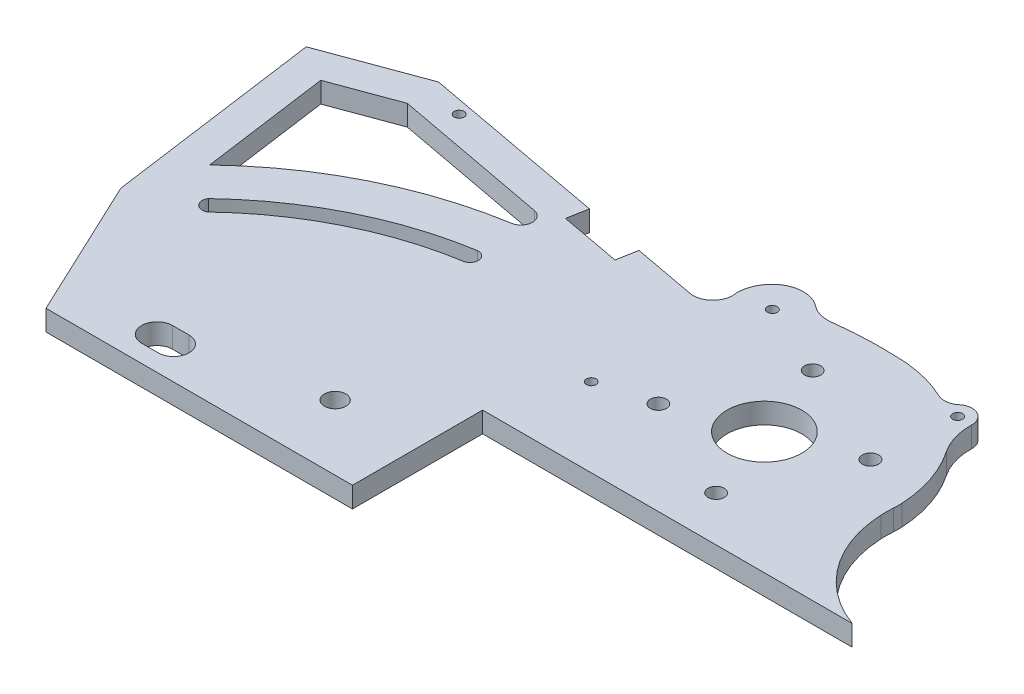
SolidWorks part; units mm, degrees
ref_plane "Front Plane" through (0, 0, 0) normal (0, 0, 1) x (1, 0, 0)
ref_plane "Top Plane" through (0, 0, 0) normal (0, 1, 0) x (1, 0, 0)
ref_plane "Right Plane" through (0, 0, 0) normal (1, 0, 0) x (0, 0, -1)
sketch "Sketch1" plane through (0, 0, 0) normal (0, 1, 0) x (1, 0, 0)
  line L0 (-48.99, 25.5713) -> (-67.7205, 29.0455)
  line L1 (-142.6426, 42.9422) -> (-143.5111, 38.2596) construction
  line L2 (-49.2049, -37.6819) -> (-49.2049, -77.8139)
  line L3 (-49.2049, -77.8139) -> (-76.5633, -77.8139)
  line L4 (-142.7166, 32.6227) -> (-162.215, 25.4248)
  line L5 (-162.215, 25.4248) -> (-156.7262, -14.2919)
  line L6 (-49.2049, -37.6819) -> (45.278, -37.6819)
  line L7 (-143.6125, 43.1221) -> (-173.3978, 32.1269)
  line L8 (-173.3978, 32.1269) -> (-164.2302, -34.2094)
  line L9 (-94.5199, 23.5914) -> (-142.7166, 32.6227)
  line L10 (-106.3396, 29.7503) -> (-50.148, 19.3278) construction
  line L11 (-143.6515, 36.6711) -> (-145.7426, 42.3358) construction
  line L12 (-50.148, 19.3278) -> (-48.99, 25.5713) construction
  line L13 (-143.6515, 36.6711) -> (-172.5514, 26.0027) construction
  line L14 (-123.3865, 39.3706) -> (-105.1816, 35.9938)
  line L15 (-142.7166, 32.6227) -> (-141.2552, 40.5019) construction
  line L18 (-86.451, 32.5197) -> (-87.6091, 26.2762)
  line L19 (-68.8786, 22.802) -> (-67.7205, 29.0455)
  line L20 (-86.451, 32.5197) -> (-105.1816, 35.9938)
  line L21 (-87.6091, 26.2762) -> (-68.8786, 22.802)
  line L22 (-164.2302, -34.2094) -> (-143.6929, -77.8139)
  line L23 (-143.6929, -77.8139) -> (-76.5633, -77.8139)
  line L24 (-114.5088, -67.653) -> (-119.5888, -67.653) construction
  line L25 (-114.5088, -72.4155) -> (-119.5888, -72.4155)
  line L26 (-114.5088, -62.8905) -> (-119.5888, -62.8905)
  line L29 (0, 0) -> (-57.1922, -21.2464) construction
  line L30 (-117.0488, -67.653) -> (-117.0488, -101.5353) construction
  line L31 (-49.2049, -37.6819) -> (45.278, -37.6819) construction
  line L32 (-49.2049, -37.6819) -> (45.278, -37.6819) construction
  line L33 (-49.2049, -37.6819) -> (45.278, -37.6819) construction
  line L34 (45.278, -37.6819) -> (64.7267, -37.6819)
  line L35 (-123.3865, 39.3706) -> (-143.6125, 43.1221)
  arc A0 (-48.99, 25.5713) -> (-41.3602, 32.7203) centre (-47.3631, 31.4809) ccw
  circle A1 centre (-131.8085, 37.7035) radius 1.524
  arc A2 (40.3286, 2.1532) -> (33.4191, 22.6758) centre (0, 0) ccw
  circle A3 centre (-131.8085, 37.7035) radius 1.1303 construction
  arc A4 (0, 40.386) -> (-18.9447, 39.5692) centre (-4.6204, -72.5606) ccw
  arc A5 (-38.2002, 40.515) -> (-41.3602, 32.7203) centre (-30.3114, 32.779) ccw
  arc A6 (-114.5088, -72.4155) -> (-114.5088, -62.8905) centre (-114.5088, -67.653) ccw
  circle A7 centre (-31.3995, 33.846) radius 1.524
  circle A8 centre (-31.3995, 33.846) radius 6.35 construction
  arc A9 (-25.5638, 41.374) -> (-38.2002, 40.515) centre (-31.3995, 33.846) ccw
  circle A10 centre (-23.7889, -8.9021) radius 2.4892
  arc A11 (-25.5638, 41.374) -> (-18.9447, 39.5692) centre (-20.0791, 48.4493) ccw
  circle A12 centre (8.9021, -23.7889) radius 2.4892
  circle A13 centre (-8.9021, 23.7889) radius 2.4892
  circle A14 centre (23.7889, 8.9021) radius 2.4892
  circle A15 centre (0, 0) radius 11.5228
  circle A16 centre (-8.9021, 23.7889) radius 6.35 construction
  arc A17 (-94.6028, 16.657) -> (-94.5199, 23.5914) centre (-95.1682, 20.1315) ccw
  arc A18 (-156.7262, -14.2919) -> (-94.6028, 16.657) centre (-75.7968, -98.9161) cw
  arc A19 (-119.5888, -62.8905) -> (-119.5888, -72.4155) centre (-119.5888, -67.653) ccw
  circle A20 centre (-23.7889, -8.9021) radius 6.35 construction
  circle A21 centre (8.9021, -23.7889) radius 6.5263 construction
  circle A22 centre (23.7889, 8.9021) radius 6.3812 construction
  circle A23 centre (-114.5088, -67.653) radius 76.2 construction
  circle A24 centre (-74.6049, -57.7479) radius 3.302
  circle A25 centre (-40.0207, -13.3674) radius 1.524
  arc A26 (40.304, -0.5649) -> (40.3286, 2.1532) centre (18.5528, 0.9906) ccw
  arc A27 (40.304, -0.5649) -> (40.2565, -4.3649) centre (72.5057, -2.8677) ccw
  arc A28 (64.7267, -37.6819) -> (40.2565, -4.3649) centre (77.5287, -2.6345) cw
  circle A29 centre (-40.0207, -13.3674) radius 4.2393 construction
  arc A30 (-147.9485, -23.4703) -> (-92.5631, 4.1219) centre (-75.7968, -98.9161) cw
  arc A31 (-144.4375, -27.1417) -> (-91.7472, -0.8921) centre (-75.7968, -98.9161) cw
  arc A32 (-147.9485, -23.4703) -> (-144.4375, -27.1417) centre (-145.815, -24.9444) ccw
  arc A33 (-91.7472, -0.8921) -> (-92.5631, 4.1219) centre (-92.3612, 1.5814) ccw
  arc A34 (30.1715, 33.7352) -> (22.862, 37.2438) centre (25.7279, 33.846) ccw
  circle A35 centre (25.7279, 33.846) radius 1.524
  arc A36 (17.2569, 36.5134) -> (22.862, 37.2438) centre (19.4911, 41.2406) ccw
  arc A37 (30.1715, 33.7352) -> (33.4191, 22.6758) centre (49.0256, 33.2653) ccw
  arc A38 (17.2569, 36.5134) -> (0, 40.386) centre (0, 0) ccw
  point P62 (-117.0488, -67.653)
  dimension "D1" = 31.75
  dimension "D2" = 12.7
  dimension "D3" = 19.05
  dimension "D6" = 3.048
  dimension "D11" = 152.4
  dimension "D12" = 6.604
  dimension "D13" = 3.048
  dimension "D8" = 3.048
  dimension "D14" = 8.89
  dimension "D4" = 95.25
  dimension "D5" = 12.7
  dimension "D7" = 5.08
  dimension "D9" = 19.05
  dimension "D10" = 6.35
extrude "Boss-Extrude1" add sketch "Sketch1" along normal blind 6.35
chamfer "Chamfer1" distance 1.905 angle 45 4 edges at (-40.0207, 0, 14.8914) (-31.3995, 0, -32.322) (-131.8085, 0, -36.1795) (25.7279, 0, -32.322)
sketch "Sketch2" plane through (1.7978, 0, -9.6927) normal (0.1824, 0, -0.9832) x (-0.9832, 0, -0.1824)
  line L0 (71.8819, 3.175) -> (90.9319, 3.175) construction
  line L1 (71.8819, 6.35) -> (71.8819, 0) construction
  line L2 (90.9319, 6.35) -> (90.9319, 0) construction
  line L3 (81.4069, 6.35) -> (81.4069, 0) construction
  line L4 (71.8819, 6.35) -> (90.9319, 6.35) construction
  line L5 (71.8819, 0) -> (90.9319, 0) construction
  circle A0 centre (81.4069, 3.175) radius 1.1303
  dimension "D1" = 2.2606
extrude "Cut-Extrude1" cut sketch "Sketch2" against normal blind 12.7
